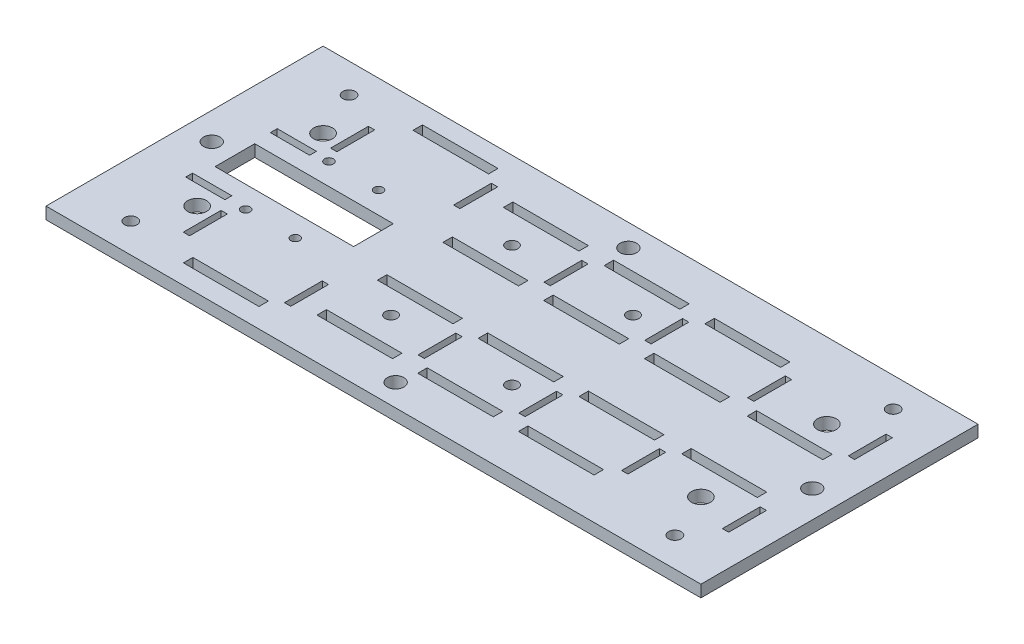
SolidWorks part; units mm, degrees
material "Thornel VCB-20 Carbon Cloth"
ref_plane "Front Plane" through (0, 0, 0) normal (0, 0, 1) x (1, 0, 0)
ref_plane "Top Plane" through (0, 0, 0) normal (0, 1, 0) x (1, 0, 0)
ref_plane "Right Plane" through (0, 0, 0) normal (1, 0, 0) x (0, 0, -1)
sketch "Sketch1" plane through (0, 0, 0) normal (0, 1, 0) x (1, 0, 0)
  line L0 (82.55, -34.925) -> (82.55, 34.925)
  line L1 (82.55, -34.925) -> (-82.55, -34.925)
  line L2 (82.55, 34.925) -> (-82.55, 34.925)
  line L3 (-82.55, -34.925) -> (-82.55, 34.925)
  line L4 (82.55, -34.925) -> (-82.55, 34.925) construction
  line L5 (82.55, 34.925) -> (-82.55, -34.925) construction
  point P1 (0, 0)
  dimension "D1" = 165.1
  dimension "D2" = 69.85
extrude "Boss-Extrude1" add sketch "Sketch1" along normal blind 3
sketch "Sketch6" plane through (0, 0, 0) normal (0, -1, 0) x (1, 0, 0)
  line L0 (-82.55, -34.925) -> (-82.55, 34.925) construction
  line L1 (-69.85, 5) -> (-34.925, 5)
  line L2 (-69.85, 5) -> (-69.85, -5)
  line L3 (-69.85, -5) -> (-34.925, -5)
  line L4 (-34.925, 5) -> (-34.925, -5)
  circle A0 centre (-15.25, 15.25) radius 1.5
  circle A1 centre (15.25, 15.25) radius 1.5
  circle A2 centre (-15.25, -15.25) radius 1.5
  circle A3 centre (15.25, -15.25) radius 1.5
  point P8 (-34.925, 0)
  dimension "D5" = 3
  dimension "D6" = 3
  dimension "D7" = 3
  dimension "D8" = 3
  dimension "D1" = 34.925
  dimension "D2" = 10
  dimension "D3" = 12.7
  dimension "D9" = 15.25
  dimension "D10" = 15.25
  dimension "D11" = 15.25
  dimension "D12" = 15.25
  dimension "D13" = 15.25
  dimension "D14" = 15.25
  dimension "D15" = 15.25
  dimension "D16" = 15.25
extrude "Cut-Extrude1" cut sketch "Sketch6" against normal up to next
sketch "Sketch7" plane through (0, 3, 0) normal (0, 1, 0) x (1, 0, 0)
  line L0 (-82.55, 34.925) -> (-82.55, -34.925) construction
  line L1 (82.55, -34.925) -> (82.55, 34.925) construction
  line L2 (-82.55, -34.925) -> (82.55, -34.925) construction
  line L3 (82.55, 34.925) -> (-82.55, 34.925) construction
  circle A0 centre (-77.47, 29.845) radius 1.5
  circle A1 centre (-77.47, -29.845) radius 1.5
  circle A2 centre (77.47, -29.845) radius 1.5
  circle A3 centre (77.47, 29.845) radius 1.5
  dimension "D9" = 3
  dimension "D10" = 3
  dimension "D11" = 3
  dimension "D12" = 3
  dimension "D1" = 5.08
  dimension "D2" = 5.08
  dimension "D3" = 5.08
  dimension "D4" = 5.08
  dimension "D5" = 5.08
  dimension "D6" = 5.08
  dimension "D7" = 5.08
  dimension "D8" = 5.08
sketch "Sketch8" plane through (0, 3, 0) normal (0, 1, 0) x (1, 0, 0)
  line L0 (-82.55, -34.925) -> (82.55, -34.925) construction
  line L1 (-82.55, 34.925) -> (-82.55, -34.925) construction
  line L2 (82.55, -34.925) -> (82.55, 34.925) construction
  line L3 (82.55, 34.925) -> (-82.55, 34.925) construction
  circle A0 centre (-63.5, -15.875) radius 2.3813
  circle A1 centre (-63.5, 15.875) radius 2.3813
  circle A2 centre (63.5, 15.875) radius 2.3813
  circle A3 centre (63.5, -15.875) radius 2.3813
  dimension "D1" = 4.7625
  dimension "D4" = 4.7625
  dimension "D5" = 4.7625
  dimension "D6" = 4.7625
  dimension "D2" = 19.05
  dimension "D3" = 19.05
  dimension "D7" = 19.05
  dimension "D8" = 19.05
  dimension "D9" = 19.05
  dimension "D10" = 19.05
  dimension "D11" = 19.05
  dimension "D12" = 19.05
extrude "Cut-Extrude3" cut sketch "Sketch8" against normal up to next
sketch "Sketch9" plane through (0, 3, 0) normal (0, 1, 0) x (1, 0, 0)
  line L0 (-82.55, 34.925) -> (-82.55, -34.925) construction
  line L1 (82.55, -34.925) -> (82.55, 34.925) construction
  circle A0 centre (-75.692, 0) radius 2.0828
  circle A1 centre (75.692, 0) radius 2.0828
  dimension "D1" = 6.858
  dimension "D2" = 6.858
extrude "Cut-Extrude5" cut sketch "Sketch9" against normal blind 5.08
sketch "Sketch10" plane through (0, 3, 0) normal (0, 1, 0) x (1, 0, 0)
  line L0 (-82.55, -34.925) -> (82.55, -34.925) construction
  line L1 (82.55, 34.925) -> (-82.55, 34.925) construction
  circle A0 centre (0, -29.337) radius 2.0828
  circle A1 centre (0, 29.337) radius 2.0828
  dimension "D1" = 5.588
  dimension "D2" = 5.588
extrude "Cut-Extrude6" cut sketch "Sketch10" against normal blind 5.08 contours A1 | A0
sketch "Sketch11" plane through (0, 3, 0) normal (0, 1, 0) x (1, 0, 0)
  line L1 (-44.1375, 10.5) -> (-56.6375, 10.5) construction
  line L2 (-44.1375, 10.5) -> (-44.1375, -10.5) construction
  line L3 (-44.1375, -10.5) -> (-56.6375, -10.5) construction
  line L4 (-56.6375, 10.5) -> (-56.6375, -10.5) construction
  line L5 (-44.1375, 10.5) -> (-56.6375, -10.5) construction
  line L6 (-44.1375, -10.5) -> (-56.6375, 10.5) construction
  line L7 (-34.925, 5) -> (-69.85, 5) construction
  circle A0 centre (-56.6375, 10.5) radius 1.125
  circle A1 centre (-44.1375, 10.5) radius 1.125
  circle A2 centre (-44.1375, -10.5) radius 1.125
  circle A3 centre (-56.6375, -10.5) radius 1.125
  point P0 (-50.3875, 0)
  point P9 (-52.3875, 5)
  dimension "D4" = 2.25
  dimension "D5" = 2.25
  dimension "D6" = 2.25
  dimension "D7" = 2.25
  dimension "D1" = 12.5
  dimension "D2" = 21
  dimension "D3" = 2
extrude "Cut-Extrude7" cut sketch "Sketch11" against normal blind 41.91
sketch "Sketch12" plane through (0, 0, 0) normal (0, -1, 0) x (1, 0, 0)
  line L0 (-24.5963, 23.3735) -> (-5.5463, 23.3735) construction
  line L1 (-24.5963, 24.5641) -> (-5.5463, 24.5641)
  line L2 (-24.5963, 24.5641) -> (-24.5963, 22.1829)
  line L3 (-24.5963, 22.1829) -> (-5.5463, 22.1829)
  line L4 (-5.5463, 24.5641) -> (-5.5463, 22.1829)
  line L5 (-15.0713, 24.5641) -> (-15.0713, 22.1829)
  line L6 (0.8037, 24.5641) -> (0.8037, 22.1829)
  line L7 (0.8037, 24.5641) -> (19.8537, 24.5641)
  line L8 (19.8537, 24.5641) -> (19.8537, 22.1829)
  line L9 (0.8037, 22.1829) -> (19.8537, 22.1829)
  line L10 (26.2037, 24.5641) -> (26.2037, 22.1829)
  line L11 (26.2037, 24.5641) -> (45.2537, 24.5641)
  line L12 (45.2537, 24.5641) -> (45.2537, 22.1829)
  line L13 (26.2037, 22.1829) -> (45.2537, 22.1829)
  line L14 (0.8037, 9.3241) -> (0.8037, 6.9429)
  line L15 (0.8037, 9.3241) -> (19.8537, 9.3241)
  line L16 (19.8537, 9.3241) -> (19.8537, 6.9429)
  line L17 (0.8037, 6.9429) -> (19.8537, 6.9429)
  line L18 (26.2037, 9.3241) -> (26.2037, 6.9429)
  line L19 (26.2037, 9.3241) -> (45.2537, 9.3241)
  line L20 (45.2537, 9.3241) -> (45.2537, 6.9429)
  line L21 (26.2037, 6.9429) -> (45.2537, 6.9429)
  line L22 (-24.5963, 9.3241) -> (-24.5963, 6.9429)
  line L23 (-24.5963, 9.3241) -> (-5.5463, 9.3241)
  line L24 (-5.5463, 9.3241) -> (-5.5463, 6.9429)
  line L25 (-24.5963, 6.9429) -> (-5.5463, 6.9429)
  line L26 (-24.5963, 24.5641) -> (0.8037, 24.5641) construction
  line L27 (-71.2714, 9.2531) -> (-61.3765, 9.2531)
  line L28 (-24.5963, -24.8071) -> (0.8037, -24.8071) construction
  line L29 (-24.5963, -23.6165) -> (-5.5463, -23.6165) construction
  line L30 (-24.5963, -7.1859) -> (-5.5463, -7.1859)
  line L31 (-5.5463, -9.5671) -> (-5.5463, -7.1859)
  line L32 (-24.5963, -9.5671) -> (-5.5463, -9.5671)
  line L33 (-24.5963, -9.5671) -> (-24.5963, -7.1859)
  line L34 (26.2037, -7.1859) -> (45.2537, -7.1859)
  line L35 (45.2537, -9.5671) -> (45.2537, -7.1859)
  line L36 (26.2037, -9.5671) -> (45.2537, -9.5671)
  line L37 (26.2037, -9.5671) -> (26.2037, -7.1859)
  line L38 (0.8037, -7.1859) -> (19.8537, -7.1859)
  line L39 (19.8537, -9.5671) -> (19.8537, -7.1859)
  line L40 (0.8037, -9.5671) -> (19.8537, -9.5671)
  line L41 (0.8037, -9.5671) -> (0.8037, -7.1859)
  line L42 (26.2037, -22.4259) -> (45.2537, -22.4259)
  line L43 (45.2537, -24.8071) -> (45.2537, -22.4259)
  line L44 (26.2037, -24.8071) -> (45.2537, -24.8071)
  line L45 (26.2037, -24.8071) -> (26.2037, -22.4259)
  line L46 (0.8037, -22.4259) -> (19.8537, -22.4259)
  line L47 (19.8537, -24.8071) -> (19.8537, -22.4259)
  line L48 (0.8037, -24.8071) -> (19.8537, -24.8071)
  line L49 (0.8037, -24.8071) -> (0.8037, -22.4259)
  line L50 (-15.0713, -24.8071) -> (-15.0713, -22.4259)
  line L51 (-5.5463, -24.8071) -> (-5.5463, -22.4259)
  line L52 (-24.5963, -22.4259) -> (-5.5463, -22.4259)
  line L53 (-24.5963, -24.8071) -> (-24.5963, -22.4259)
  line L54 (-24.5963, -24.8071) -> (-5.5463, -24.8071)
  line L55 (22.2349, 10.991) -> (22.2349, 20.516)
  line L56 (-3.1651, 10.991) -> (-1.5776, 10.991)
  line L57 (-3.1651, 10.991) -> (-3.1651, 20.516)
  line L58 (-3.1651, 20.516) -> (-1.5776, 20.516)
  line L59 (-1.5776, 10.991) -> (-1.5776, 20.516)
  line L60 (-3.1651, 10.991) -> (-1.5776, 20.516) construction
  line L61 (-3.1651, 20.516) -> (-1.5776, 10.991) construction
  line L62 (22.2349, 10.991) -> (23.8224, 10.991)
  line L63 (23.8224, 10.991) -> (23.8224, 20.516)
  line L64 (22.2349, 20.516) -> (23.8224, 20.516)
  line L65 (-3.1651, 10.991) -> (22.2349, 10.991) construction
  line L66 (-3.1651, -20.759) -> (-1.5776, -20.759)
  line L67 (-1.5776, -11.234) -> (-1.5776, -20.759)
  line L68 (-3.1651, -11.234) -> (-1.5776, -11.234)
  line L69 (-3.1651, -11.234) -> (-3.1651, -20.759)
  line L70 (22.2349, -11.234) -> (23.8224, -11.234)
  line L71 (23.8224, -11.234) -> (23.8224, -20.759)
  line L72 (22.2349, -20.759) -> (23.8224, -20.759)
  line L73 (22.2349, -11.234) -> (22.2349, -20.759)
  line L78 (51.6896, 8.9006) -> (51.6896, 6.5194)
  line L79 (51.6896, 8.9006) -> (70.7396, 8.9006)
  line L80 (70.7396, 8.9006) -> (70.7396, 6.5194)
  line L81 (51.6896, 6.5194) -> (70.7396, 6.5194)
  line L82 (-70.3121, -11.1231) -> (-60.4172, -11.1231)
  line L83 (64.3896, -0.545) -> (-18.1604, -0.545) construction
  line L84 (-70.3121, -11.1231) -> (-70.3121, -9.3903)
  line L85 (51.6896, -7.6094) -> (70.7396, -7.6094)
  line L86 (70.7396, -9.9906) -> (70.7396, -7.6094)
  line L87 (51.6896, -9.9906) -> (70.7396, -9.9906)
  line L88 (51.6896, -9.9906) -> (51.6896, -7.6094)
  line L93 (73.1208, 10.5675) -> (73.1208, 20.0925)
  line L94 (47.7208, 10.5675) -> (49.3083, 10.5675)
  line L95 (47.7208, 10.5675) -> (47.7208, 20.0925)
  line L96 (47.7208, 20.0925) -> (49.3083, 20.0925)
  line L97 (49.3083, 10.5675) -> (49.3083, 20.0925)
  line L98 (47.7208, 10.5675) -> (49.3083, 20.0925) construction
  line L99 (47.7208, 20.0925) -> (49.3083, 10.5675) construction
  line L100 (73.1208, 10.5675) -> (74.7083, 10.5675)
  line L101 (74.7083, 10.5675) -> (74.7083, 20.0925)
  line L102 (73.1208, 20.0925) -> (74.7083, 20.0925)
  line L103 (47.7208, 10.5675) -> (73.1208, 10.5675) construction
  line L104 (47.7208, -21.1825) -> (49.3083, -21.1825)
  line L105 (49.3083, -11.6575) -> (49.3083, -21.1825)
  line L106 (47.7208, -11.6575) -> (49.3083, -11.6575)
  line L107 (47.7208, -11.6575) -> (47.7208, -21.1825)
  line L108 (73.1208, -11.6575) -> (74.7083, -11.6575)
  line L109 (74.7083, -11.6575) -> (74.7083, -21.1825)
  line L110 (73.1208, -21.1825) -> (74.7083, -21.1825)
  line L111 (73.1208, -11.6575) -> (73.1208, -21.1825)
  line L112 (-70.3121, -9.3903) -> (-60.4172, -9.3903)
  line L113 (-60.4172, -11.1231) -> (-60.4172, -9.3903)
  line L114 (-52.8291, -27.8715) -> (-33.7791, -27.8715)
  line L115 (-33.7791, -30.2527) -> (-33.7791, -27.8715)
  line L116 (-52.8291, -30.2527) -> (-33.7791, -30.2527)
  line L117 (-52.8291, -30.2527) -> (-52.8291, -27.8715)
  line L118 (-70.3121, -11.1231) -> (-60.4172, -9.3903) construction
  line L123 (-59.3265, -23.1262) -> (-57.739, -23.1262)
  line L124 (-57.739, -13.6012) -> (-57.739, -23.1262)
  line L125 (-59.3265, -13.6012) -> (-57.739, -13.6012)
  line L126 (-59.3265, -13.6012) -> (-59.3265, -23.1262)
  line L127 (-31.3979, -16.6796) -> (-29.8104, -16.6796)
  line L128 (-29.8104, -16.6796) -> (-29.8104, -26.2046)
  line L129 (-31.3979, -26.2046) -> (-29.8104, -26.2046)
  line L130 (-31.3979, -16.6796) -> (-31.3979, -26.2046)
  line L131 (-70.3121, -9.3903) -> (-60.4172, -11.1231) construction
  line L132 (-71.2714, 9.2531) -> (-71.2714, 10.9859)
  line L133 (-31.3979, 16.4366) -> (-31.3979, 25.9616)
  line L134 (-31.3979, 25.9616) -> (-29.8104, 25.9616)
  line L135 (-29.8104, 16.4366) -> (-29.8104, 25.9616)
  line L136 (-31.3979, 16.4366) -> (-29.8104, 16.4366)
  line L137 (-59.5464, 13.798) -> (-59.5464, 23.323)
  line L138 (-59.5464, 13.798) -> (-57.9589, 13.798)
  line L139 (-57.9589, 13.798) -> (-57.9589, 23.323)
  line L140 (-59.5464, 23.323) -> (-57.9589, 23.323)
  line L145 (-71.2714, 10.9859) -> (-61.3765, 10.9859)
  line L146 (-52.8291, 30.0097) -> (-52.8291, 27.6285)
  line L147 (-52.8291, 30.0097) -> (-33.7791, 30.0097)
  line L148 (-33.7791, 30.0097) -> (-33.7791, 27.6285)
  line L149 (-52.8291, 27.6285) -> (-33.7791, 27.6285)
  line L150 (-61.3765, 9.2531) -> (-61.3765, 10.9859)
  point P8 (-65.3646, -10.2567)
  point P60 (-2.3713, 15.7535)
  point P100 (48.5146, 15.33)
  dimension "D1" = 19.05
  dimension "D2" = 2.3813
  dimension "D3" = 25.4
  dimension "D4" = 15.24
  dimension "D5" = 1.5875
  dimension "D6" = 3.175
  dimension "D7" = 9.525
  dimension "D8" = 7.62
  dimension "D9" = 25.4
extrude "Cut-Extrude8" cut sketch "Sketch12" against normal blind 21.336 contours L37 L36 L35 L34 | L88 L87 L86 L85 | L45 L44 L43 L42 | L117 L116 L115 L114 | L78 L81 L80 L79 | L10 L13 L12 L11 | L6 L9 L8 L7 | L14 L17 L16 L15 | L107 L104 L105 L106 | L109 L110 L111 L108 | L71 L72 L73 L70 | L40 L39 L38 L41 | L48 L47 L46 L49 | L67 L66 L69 L68 | L52 L51 L54 L53 | L30 L31 L32 L33 | L130 L129 L128 L127 | L126 L123 L124 L125 | L93 L102 L101 L100 | L97 L96 L95 L94 | L19 L20 L21 L18 | L63 L64 L55 L62 | L56 L59 L58 L57 | L25 L24 L23 L22 | L3 L4 L1 L2 | L135 L134 L133 L136 | L149 L148 L147 L146 | L139 L140 L137 L138 | L27 L150 L145 L132 | L84 L82 L113 L112 region at (10.3287, 0, 23.3735) region at (35.7287, 0, 23.3735) region at (10.3287, 0, 8.1335) region at (35.7287, 0, -8.3765) region at (35.7287, 0, -23.6165) region at (61.2146, 0, 7.71) region at (61.2146, 0, -8.8) region at (-43.3041, 0, -29.0621)
sketch "Sketch13" plane through (0, 0, 0) normal (0, -1, 0) x (1, 0, 0)
  line L0 (0, 18.4306) -> (0, -15.755) construction
  circle A0 centre (-68.5804, 27.5146) radius 1.5875 construction
  circle A1 centre (-68.5804, -27.5146) radius 1.5875 construction
  circle A2 centre (-68.5804, 27.5146) radius 1.5875
  circle A3 centre (-68.5804, -27.5146) radius 1.5875
  circle A4 centre (68.5804, -27.5146) radius 1.5875
  circle A5 centre (68.5804, 27.5146) radius 1.5875
extrude "Cut-Extrude10" cut sketch "Sketch13" against normal blind 28.034
